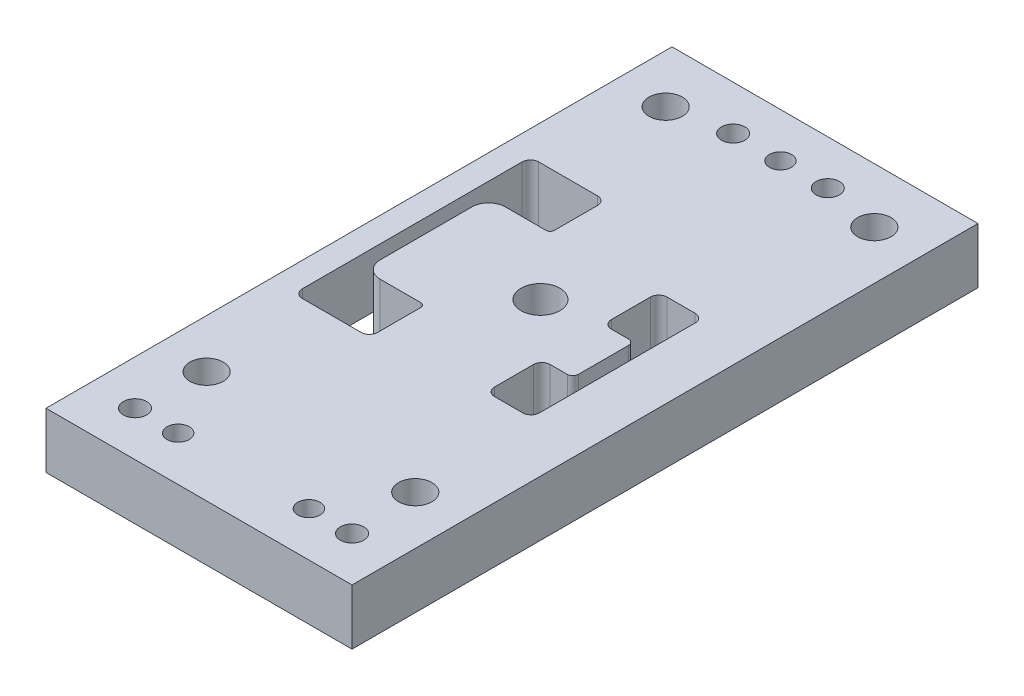
SolidWorks part; units mm, degrees
material "Plain Carbon Steel"
ref_plane "Front Plane" through (0, 0, 0) normal (0, 0, 1) x (1, 0, 0)
ref_plane "Top Plane" through (0, 0, 0) normal (0, 1, 0) x (1, 0, 0)
ref_plane "Right Plane" through (0, 0, 0) normal (1, 0, 0) x (0, 0, -1)
sketch "Sketch1" plane through (0, 0, 0) normal (0, 1, 0) x (1, 0, 0)
  line L1 (-55, -112.5) -> (55, -112.5)
  line L2 (-55, -112.5) -> (-55, 112.5)
  line L3 (-55, 112.5) -> (55, 112.5)
  line L4 (55, -112.5) -> (55, 112.5)
  line L5 (-55, -112.5) -> (55, 112.5) construction
  line L6 (-55, 112.5) -> (55, -112.5) construction
  point P0 (0, 0)
  dimension "D1" = 225
  dimension "D2" = 110
extrude "Boss-Extrude1" add sketch "Sketch1" along normal blind 20
sketch "Sketch2" plane through (0, 20, 0) normal (0, 1, 0) x (1, 0, 0)
  line L0 (-43.12, 37.73) -> (-19, 37.73) construction
  line L1 (-43.12, -17.27) -> (-19, -17.27) construction
  line L8 (-41.12, 26.73) -> (-41.12, -6.27) construction
  line L9 (-43.12, -32.27) -> (-22, -32.27)
  line L11 (-43.12, 52.73) -> (-22, 52.73)
  line L13 (-20.5, 32.73) -> (-35.12, 32.73) construction
  line L14 (-19, 37.73) -> (-19, 34.23) construction
  line L16 (-46.12, 34.73) -> (-46.12, -14.27) construction
  line L18 (-19, -17.27) -> (-19, -13.77) construction
  line L19 (-35.12, -12.27) -> (-20.5, -12.27) construction
  line L20 (-41.12, 26.73) -> (-41.12, -6.27)
  line L21 (-20.5, 32.73) -> (-35.12, 32.73)
  line L22 (-19, 49.73) -> (-19, 34.23)
  line L24 (-46.12, 49.73) -> (-46.12, -29.27)
  line L26 (-19, -29.27) -> (-19, -13.77)
  line L27 (-35.12, -12.27) -> (-20.5, -12.27)
  arc A0 (-22, 52.73) -> (-19, 49.73) centre (-22, 49.73) cw
  arc A1 (-46.12, 49.73) -> (-43.12, 52.73) centre (-43.12, 49.73) cw
  arc A2 (-43.12, -32.27) -> (-46.12, -29.27) centre (-43.12, -29.27) cw
  arc A3 (-22, -32.27) -> (-19, -29.27) centre (-22, -29.27) ccw
  arc A6 (-41.12, -6.27) -> (-35.12, -12.27) centre (-35.12, -6.27) ccw construction
  arc A7 (-35.12, 32.73) -> (-41.12, 26.73) centre (-35.12, 26.73) ccw construction
  arc A8 (-20.5, 32.73) -> (-19, 34.23) centre (-20.5, 34.23) ccw construction
  arc A11 (-19, -13.77) -> (-20.5, -12.27) centre (-20.5, -13.77) ccw construction
  arc A12 (-41.12, -6.27) -> (-35.12, -12.27) centre (-35.12, -6.27) ccw
  arc A13 (-35.12, 32.73) -> (-41.12, 26.73) centre (-35.12, 26.73) ccw
  arc A14 (-20.5, 32.73) -> (-19, 34.23) centre (-20.5, 34.23) ccw
  arc A17 (-19, -13.77) -> (-20.5, -12.27) centre (-20.5, -13.77) ccw
  dimension "D3" = 3
  dimension "D1" = 15
  dimension "D2" = 15
extrude "Cut-Extrude1" cut sketch "Sketch2" against normal up to next
sketch "Sketch3" plane through (0, 20, 0) normal (0, 1, 0) x (1, 0, 0)
  line L0 (22, -8.27) -> (28.13, -8.27) construction
  line L1 (19, -13.27) -> (19, -11.27) construction
  line L3 (35.13, 15.73) -> (35.13, -10.27) construction
  line L5 (19, 18.73) -> (19, 16.73) construction
  line L6 (28.13, 13.73) -> (22, 13.73) construction
  line L7 (30.13, -6.27) -> (30.13, 11.73) construction
  line L8 (22, -8.27) -> (28.13, -8.27)
  line L9 (19, -25.27) -> (19, -11.27)
  line L11 (35.13, 30.73) -> (35.13, -25.27)
  line L13 (19, 30.73) -> (19, 16.73)
  line L14 (28.13, 13.73) -> (22, 13.73)
  line L15 (30.13, -6.27) -> (30.13, 11.73)
  line L16 (22, -28.27) -> (32.13, -28.27)
  line L17 (22, 33.73) -> (32.13, 33.73)
  line L18 (19, 18.73) -> (32.13, 18.73) construction
  line L19 (32.13, -13.27) -> (19, -13.27) construction
  arc A0 (28.13, -8.27) -> (30.13, -6.27) centre (28.13, -6.27) ccw construction
  arc A1 (22, -8.27) -> (19, -11.27) centre (22, -11.27) ccw construction
  arc A4 (19, 16.73) -> (22, 13.73) centre (22, 16.73) ccw construction
  arc A5 (30.13, 11.73) -> (28.13, 13.73) centre (28.13, 11.73) ccw construction
  arc A6 (28.13, -8.27) -> (30.13, -6.27) centre (28.13, -6.27) ccw
  arc A7 (22, -8.27) -> (19, -11.27) centre (22, -11.27) ccw
  arc A10 (19, 16.73) -> (22, 13.73) centre (22, 16.73) ccw
  arc A11 (30.13, 11.73) -> (28.13, 13.73) centre (28.13, 11.73) ccw
  arc A12 (22, 33.73) -> (19, 30.73) centre (22, 30.73) ccw
  arc A13 (32.13, 33.73) -> (35.13, 30.73) centre (32.13, 30.73) cw
  arc A14 (32.13, -28.27) -> (35.13, -25.27) centre (32.13, -25.27) ccw
  arc A15 (22, -28.27) -> (19, -25.27) centre (22, -25.27) cw
  dimension "D3" = 3
  dimension "D1" = 15
  dimension "D2" = 15
extrude "Cut-Extrude2" cut sketch "Sketch3" against normal up to next
sketch "Sketch4" plane through (0, 0, 0) normal (0, -1, 0) x (1, 0, 0)
  circle A0 centre (37.5, 52.27) radius 10.5 construction
  circle A1 centre (12.5, 52.27) radius 10.5 construction
  circle A2 centre (-12.5, 52.27) radius 10.5 construction
  circle A3 centre (-37.5, 52.27) radius 10.5 construction
  circle A4 centre (0, 9.77) radius 10.5 construction
  circle A5 centre (0, -30.23) radius 10.5 construction
  circle A6 centre (37.5, -72.73) radius 10.5 construction
  circle A7 centre (12.5, -72.73) radius 10.5 construction
  circle A8 centre (-12.5, -72.73) radius 10.5 construction
  circle A9 centre (-37.5, -72.73) radius 10.5 construction
  circle A10 centre (37.5, 52.27) radius 10.5
  circle A11 centre (12.5, 52.27) radius 10.5
  circle A12 centre (-12.5, 52.27) radius 10.5
  circle A13 centre (-37.5, 52.27) radius 10.5
  circle A14 centre (0, 9.77) radius 10.5
  circle A15 centre (0, -30.23) radius 10.5
  circle A16 centre (37.5, -72.73) radius 10.5
  circle A17 centre (12.5, -72.73) radius 10.5
  circle A18 centre (-12.5, -72.73) radius 10.5
  circle A19 centre (-37.5, -72.73) radius 10.5
extrude "Cut-Extrude3" cut sketch "Sketch4" against normal blind 14.2
sketch "Sketch5" plane through (0, 20, 0) normal (0, 1, 0) x (1, 0, 0)
  circle A0 centre (-37.5, 92.73) radius 6
  circle A1 centre (37.5, 92.73) radius 6
  circle A2 centre (-37.5, -72.27) radius 6
  circle A3 centre (37.5, -72.27) radius 6
  dimension "D1" = 12
extrude "Cut-Extrude4" cut sketch "Sketch5" against normal up to next
sketch "Sketch6" plane through (0, 20, 0) normal (0, 1, 0) x (1, 0, 0)
  circle A0 centre (0, 10.23) radius 7
  dimension "D1" = 14
extrude "Cut-Extrude5" cut sketch "Sketch6" against normal up to next
hole_wizard "CBORE for M8 Hex Socket Head Cap Screw1" positions "Sketch10" profile "Sketch9" counterbore size "M8" standard "ISO" end condition through all
sketch "Sketch10" plane through (0, 0, 0) normal (0, -1, 0) x (-1, 0, 0)
  line L0 (-55, -112.5) -> (-55, 112.5) construction
  line L1 (55, 112.5) -> (55, -112.5) construction
  line L2 (-55, 112.5) -> (55, 112.5) construction
  line L3 (55, -112.5) -> (-55, -112.5) construction
  point P0 (-17, 96.5)
  point P2 (17, 96.5)
  point P4 (-39, -96.5)
  point P6 (39, -96.5)
  point P21 (0, 0)
  dimension "D1" = 38
  dimension "D2" = 38
  dimension "D3" = 16
  dimension "D4" = 16
  dimension "D5" = 16
  dimension "D6" = 16
sketch "Sketch9" plane through (17, 0, -96.5) normal (1, 0, 0) x (0, 0, -1)
  line L0 (0, 0) -> (0, 20)
  line L1 (0, 20) -> (4.2, 20)
  line L3 (4.2, 20) -> (4.2, 8.6)
  line L4 (4.2, 8.6) -> (7.5, 8.6)
  line L5 (7.5, 8.6) -> (7.5, 0)
  line L7 (7.5, 0) -> (0, 0)
  line L11 (0, -6.35) -> (0, 107.95) construction
  dimension "Thru Hole Dia." = 8.4
  dimension "Thru Hole Depth" = 20
  dimension "C'Bore Dia." = 15
  dimension "C'Bore Depth" = 8.6
hole_wizard "Ø8.0mm Dowel Hole1" positions "Sketch13" profile "Sketch12" hole size "Ø8.0" standard "ISO" end condition through all
sketch "Sketch13" plane through (0, 0, 0) normal (0, -1, 0) x (-1, 0, 0)
  line L0 (-55, 112.5) -> (55, 112.5) construction
  line L1 (55, -112.5) -> (-55, -112.5) construction
  circle A2 centre (-39, -96.5) radius 7.5 construction
  circle A3 centre (39, -96.5) radius 7.5 construction
  point P0 (0, 96.5)
  point P2 (-23.5, -96.5)
  point P4 (23.5, -96.5)
  point P11 (0, 0)
  point P16 (0, 0)
  dimension "D3" = 8
  dimension "D4" = 8
  dimension "D1" = 16
  dimension "D2" = 16
sketch "Sketch12" plane through (0, 0, -96.5) normal (1, 0, 0) x (0, 0, -1)
  line L0 (0, 0) -> (0, 20)
  line L1 (0, 20) -> (4, 20)
  line L2 (4, 20) -> (4, 0)
  line L5 (4, 0) -> (0, 0)
  line L11 (0, -6.35) -> (0, 107.95) construction
  dimension "Thru Hole Dia." = 8
  dimension "Thru Hole Depth" = 20
